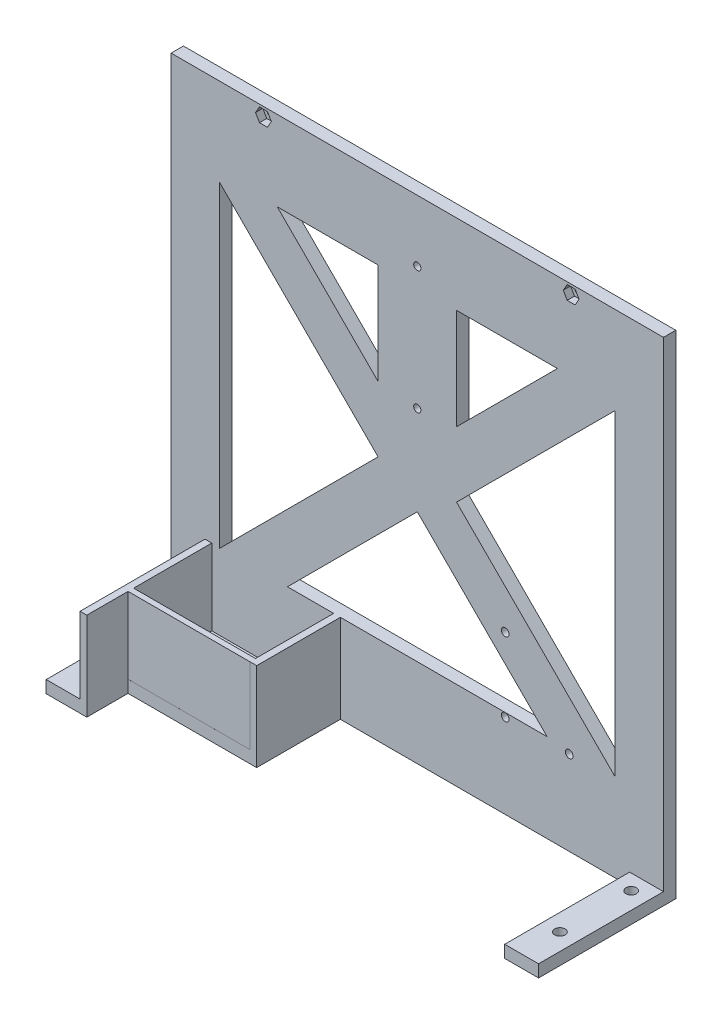
SolidWorks part; units mm, degrees
ref_plane "Front" through (0, 0, 0) normal (0, 0, 1) x (1, 0, 0)
ref_plane "Top" through (0, 0, 0) normal (0, 1, 0) x (1, 0, 0)
ref_plane "Right" through (0, 0, 0) normal (1, 0, 0) x (0, 0, -1)
sketch "Sketch1" plane through (0, 0, 0) normal (0, 0, 1) x (1, 0, 0)
  line L0 (-81.5432, 65.3545) -> (-81.5432, -65.3545)
  line L1 (-101.6, 101.6) -> (101.6, 101.6)
  line L2 (-101.6, 101.6) -> (-101.6, -101.6)
  line L3 (-101.6, -101.6) -> (101.6, -101.6)
  line L4 (101.6, 101.6) -> (101.6, -101.6)
  line L5 (-101.6, 101.6) -> (101.6, -101.6) construction
  line L6 (-101.6, -101.6) -> (101.6, 101.6) construction
  line L7 (0, -55) -> (0, 55) construction
  line L8 (-81.5432, -65.3545) -> (-16.1887, 0)
  line L9 (-16.1887, 0) -> (-81.5432, 65.3545)
  line L10 (55, 0) -> (-55, 0) construction
  line L11 (16.1887, 0) -> (81.5432, 65.3545)
  line L12 (81.5432, -65.3545) -> (16.1887, 0)
  line L13 (81.5432, 65.3545) -> (81.5432, -65.3545)
  line L14 (-16.1887, 68.5673) -> (-16.1887, 26.9408)
  line L15 (-16.1887, 26.9408) -> (-57.8152, 68.5673)
  line L16 (-57.8152, 68.5673) -> (-16.1887, 68.5673)
  line L17 (16.1887, 26.9408) -> (57.8152, 68.5673)
  line L18 (16.1887, 68.5673) -> (16.1887, 26.9408)
  line L19 (57.8152, 68.5673) -> (16.1887, 68.5673)
  line L20 (-53.5883, -65.1346) -> (0, -11.5463)
  line L21 (0, -11.5463) -> (53.5883, -65.1346)
  line L22 (53.5883, -65.1346) -> (-53.5883, -65.1346)
  circle A0 centre (0, 76.2) radius 1.5
  circle A2 centre (0, 25.4) radius 1.5
  circle A3 centre (-63.5, 97.79) radius 1.5
  circle A4 centre (63.5, 97.79) radius 1.5
  point P0 (0, 0)
  dimension "D3" = 3
  dimension "D4" = 50.8
  dimension "D6" = 19.05
  dimension "D7" = 3
  dimension "D9" = 63.5
  dimension "D1" = 203.2
  dimension "D2" = 203.2
  dimension "D5" = 25.4
  dimension "D8" = 3.81
extrude "Boss-Extrude1" add sketch "Sketch1" along normal blind 5.08 contours L4 L1 L2 L3 A2 A0 L19 L17 L18 L9 L8 L0 L11 L13 L12 L15 L16 L14 L21 L22 L20 region at (0, 1.383, 0)
sketch "Sketch2" plane through (0, 0, 5.08) normal (0, 0, 1) x (1, 0, 0)
  line L0 (-101.6, -101.6) -> (101.6, -101.6) construction
  line L1 (-101.6, -101.6) -> (-87.63, -101.6)
  line L2 (-101.6, -101.6) -> (-101.6, -96.52)
  line L3 (-101.6, -96.52) -> (-87.63, -96.52)
  line L4 (-87.63, -101.6) -> (-87.63, -96.52)
  line L5 (0, -55) -> (0, 55) construction
  line L6 (101.6, -96.52) -> (87.63, -96.52)
  line L7 (87.63, -101.6) -> (87.63, -96.52)
  line L8 (101.6, -101.6) -> (87.63, -101.6)
  line L9 (101.6, -101.6) -> (101.6, -96.52)
  line L10 (53.5883, -65.1346) -> (-53.5883, -65.1346) construction
  line L11 (-87.63, -96.52) -> (-31.75, -96.52)
  line L12 (-87.63, -96.52) -> (-87.63, -101.6)
  line L13 (-87.63, -101.6) -> (-31.75, -101.6)
  line L14 (-31.75, -96.52) -> (-31.75, -101.6)
  line L15 (-87.63, -96.52) -> (-84.836, -96.52)
  line L16 (-87.63, -96.52) -> (-87.63, -65.1346)
  line L17 (-87.63, -65.1346) -> (-84.836, -65.1346)
  line L18 (-84.836, -96.52) -> (-84.836, -65.1346)
  line L19 (-31.75, -96.52) -> (-34.544, -96.52)
  line L20 (-31.75, -96.52) -> (-31.75, -65.1346)
  line L21 (-31.75, -65.1346) -> (-34.544, -65.1346)
  line L22 (-34.544, -96.52) -> (-34.544, -65.1346)
  line M10 (-101.6, -101.6) -> (101.6, -101.6)
  dimension "D1" = 5.08
  dimension "D2" = 55.88
  dimension "D3" = 50.292
  dimension "D4" = 13.97
  dimension "D5" = 31.75
extrude "Boss-Extrude2" add sketch "Sketch2" along normal blind 51.562 contours L4 L3 L2 M10 | L14 L11 L4 M10 | L9 L6 L7 M10 | L16 L15 L18 L17 | L20 L19 L22 L21 region at (-94.615, -99.06, 5.08) region at (94.615, -99.06, 5.08) region at (-59.69, -99.06, 5.08)
sketch "Sketch3" plane through (0, -96.52, 0) normal (0, 1, 0) x (1, 0, 0)
  line L4 (0, -55) -> (0, 55) construction
  line L10 (-101.6, -5.08) -> (-87.63, -5.08) construction
  line L11 (-101.6, -56.642) -> (-101.6, -5.08) construction
  circle A0 centre (-94.615, -11.43) radius 2.159
  circle A1 centre (94.615, -11.43) radius 2.159
  circle A2 centre (-94.615, -40.84) radius 2.159
  circle A3 centre (94.615, -40.84) radius 2.159
  dimension "D1" = 4.318
  dimension "D4" = 29.41
  dimension "D5" = 4.318
  dimension "D6" = 4.318
  dimension "D2" = 6.35
  dimension "D3" = 6.985
extrude "Cut-Extrude1" cut sketch "Sketch3" against normal up to next contours A0 | A1 | A3 | A2 | A2 | A3 region at (-94.615, -96.52, 11.43) region at (94.615, -96.52, 11.43) region at (-94.615, -96.52, 40.84) region at (94.615, -96.52, 40.84)
sketch "Sketch7" plane through (0, 0, 5.08) normal (0, 0, 1) x (1, 0, 0)
  circle A0 centre (36.2876, -66.7853) radius 1.5875
  circle A1 centre (36.2876, -36.4323) radius 1.5875
  circle A3 centre (62.7036, -66.7853) radius 1.5875
  dimension "D1" = 3.175
  dimension "D2" = 30.353
  dimension "D3" = 26.416
extrude "Cut-Extrude2" cut sketch "Sketch7" against normal up to next
sketch "Sketch8" plane through (-34.544, 0, 0) normal (-1, 0, 0) x (0, 0, 1)
  line L0 (56.642, -65.1346) -> (5.08, -65.1346) construction
  line L1 (37.33, -65.1346) -> (39.63, -65.1346)
  line L2 (37.33, -65.1346) -> (37.33, -96.52)
  line L3 (37.33, -96.52) -> (39.63, -96.52)
  line L4 (39.63, -65.1346) -> (39.63, -96.52)
  line L5 (56.642, -96.52) -> (5.08, -96.52) construction
  line L7 (5.08, -96.52) -> (5.08, -65.1346) construction
  dimension "D1" = 2.3
  dimension "D2" = 32.25
extrude "Boss-Extrude6" add sketch "Sketch8" along normal up to next
sketch "Sketch10" plane through (-31.75, 0, 0) normal (1, 0, 0) x (0, 0, -1)
  line L0 (-56.642, -65.1346) -> (-5.08, -65.1346) construction
  line L1 (-56.642, -101.6) -> (-39.632, -101.6)
  line L2 (-56.642, -101.6) -> (-56.642, -65.1346)
  line L3 (-56.642, -65.1346) -> (-39.632, -65.1346)
  line L4 (-39.632, -101.6) -> (-39.632, -65.1346)
  point P7 (-56.642, -83.3673)
  dimension "D1" = 17.01
extrude "Cut-Extrude3" cut sketch "Sketch10" against normal blind 53.09
sketch "Sketch11" plane through (0, 0, 5.08) normal (0, 0, 1) x (1, 0, 0)
  line L0 (0, -31.1531) -> (0, 31.1531) construction
  line L1 (-61.869, 94.965) -> (-60.238, 97.79)
  line L2 (-60.238, 97.79) -> (-61.869, 100.615)
  line L3 (-61.869, 100.615) -> (-65.131, 100.615)
  line L4 (-65.131, 100.615) -> (-66.762, 97.79)
  line L5 (-66.762, 97.79) -> (-65.131, 94.965)
  line L6 (-65.131, 94.965) -> (-61.869, 94.965)
  line L7 (65.131, 94.965) -> (61.869, 94.965)
  line L8 (66.762, 97.79) -> (65.131, 94.965)
  line L9 (65.131, 100.615) -> (66.762, 97.79)
  line L10 (61.869, 100.615) -> (65.131, 100.615)
  line L11 (60.238, 97.79) -> (61.869, 100.615)
  line L12 (61.869, 94.965) -> (60.238, 97.79)
  circle A0 centre (-63.5, 97.79) radius 1.5 construction
  circle A1 centre (-63.5, 97.79) radius 1.5
  circle A2 centre (-63.5, 97.79) radius 2.825 construction
  circle A3 centre (63.5, 97.79) radius 2.825 construction
  circle A4 centre (63.5, 97.79) radius 1.5
  circle M36 centre (-63.5, 97.79) radius 1.5
  circle M37 centre (63.5, 97.79) radius 1.5
  dimension "D1" = 5.65
extrude "Cut-Extrude4" cut sketch "Sketch11" against normal blind 3 contours L5 L6 L1 L2 L3 L4 M36 | L12 L7 L8 L9 L10 L11 M37 region at (-63.5, 95.0513, 5.08) region at (63.5, 95.0513, 5.08)
